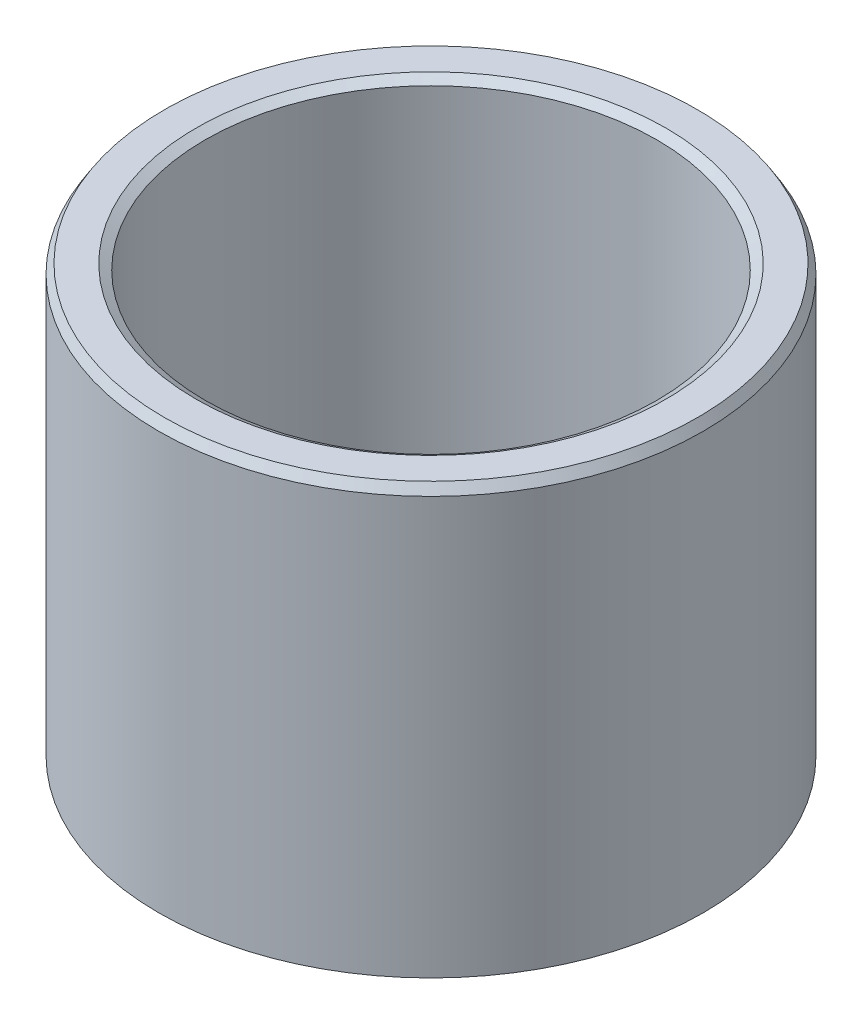
SolidWorks part; units mm, degrees
ref_plane "Front Plane" through (0, 0, 0) normal (0, 0, 1) x (1, 0, 0)
ref_plane "Top Plane" through (0, 0, 0) normal (0, 1, 0) x (1, 0, 0)
ref_plane "Right Plane" through (0, 0, 0) normal (1, 0, 0) x (0, 0, -1)
sketch "Sketch1" plane through (0, 0, 0) normal (0, 1, 0) x (1, 0, 0)
  circle A0 centre (0, 0) radius 30
  dimension "SLEEVE_OD" = 60
extrude "Boss-Extrude1" add sketch "Sketch1" along normal blind 47.5843
sketch "Sketch2" plane through (0, 0, 0) normal (0, 1, 0) x (1, 0, 0)
  circle A0 centre (0, 0) radius 24.8815
  dimension "BORE_D" = 49.763
extrude "Cut-Extrude1" cut sketch "Sketch2" along normal through all
chamfer "Chamfer1" distance 1.0068 angle 31.576 4 edges at (0, 47.5843, 24.8815) (0, 0, 24.8815) (0, 0, 30) (0, 47.5843, 30) first distance on face at (0, 47.5843, 24.8815) first distance on face at (0, 0, 24.8815) first distance on face at (0, 47.5843, 30)
